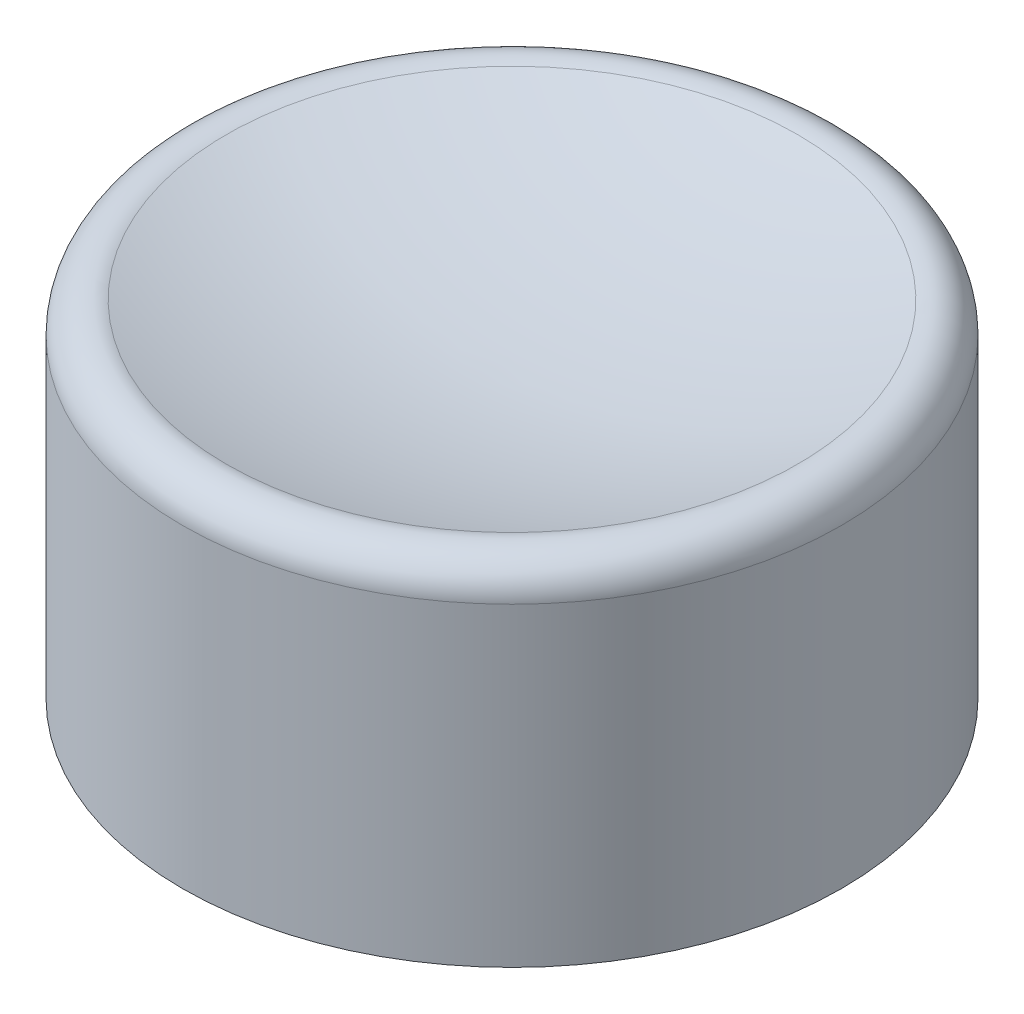
SolidWorks part; units mm, degrees
material "ABS"
ref_plane "Front Plane" through (0, 0, 0) normal (0, 0, 1) x (1, 0, 0)
ref_plane "Top Plane" through (0, 0, 0) normal (0, 1, 0) x (1, 0, 0)
ref_plane "Right Plane" through (0, 0, 0) normal (1, 0, 0) x (0, 0, -1)
sketch "Sketch1" plane through (0, 0, 0) normal (0, 1, 0) x (1, 0, 0)
  circle A0 centre (0, 0) radius 5
extrude "Boss-Extrude1" add sketch "Sketch1" along normal blind 5.5
sketch "Sketch2" plane through (0, 0, 0) normal (0, -1, 0) x (1, 0, 0)
  circle A0 centre (0, 0) radius 1.75
extrude "Cut-Extrude1" cut sketch "Sketch2" against normal blind 4
dome "Dome1" faces to dome 1 distance 1 reverse direction yes elliptical dome no face at (0, 5.5, 5) parameters "D1"=1
fillet "Fillet1" radius 0.5 1 edges at (0, 5.5, 5)
